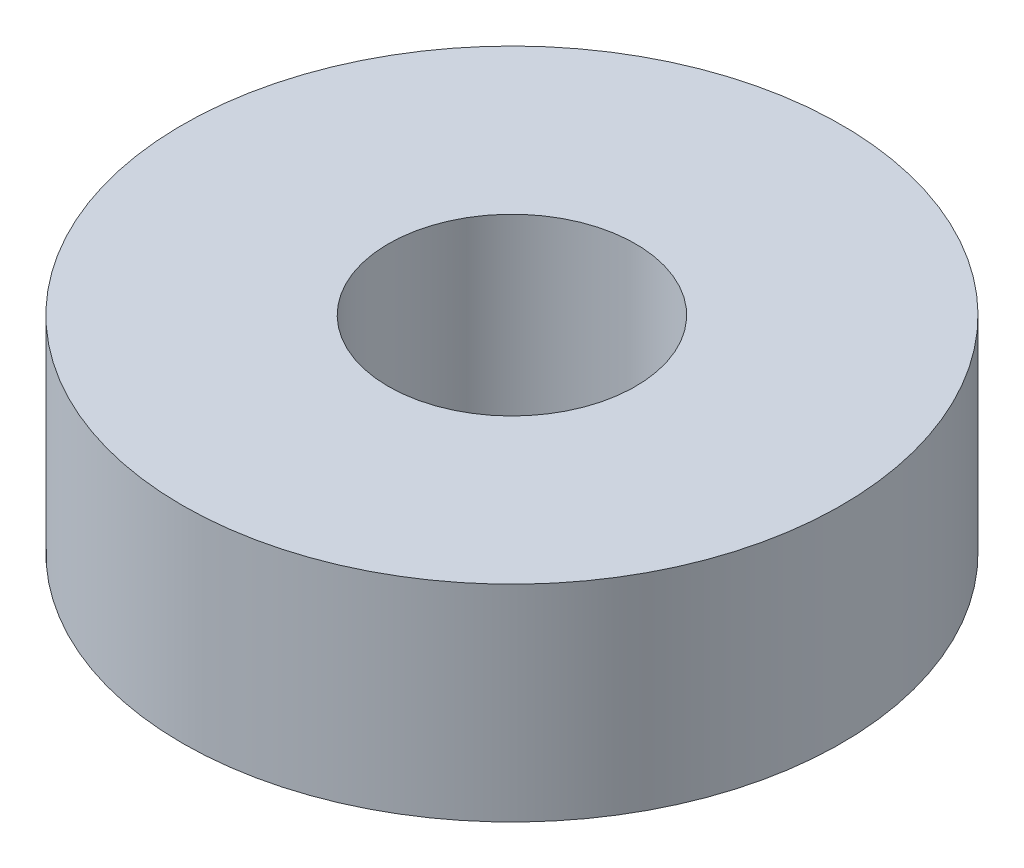
SolidWorks part; units mm, degrees
ref_plane "Front Plane" through (0, 0, 0) normal (0, 0, 1) x (1, 0, 0)
ref_plane "Top Plane" through (0, 0, 0) normal (0, 1, 0) x (1, 0, 0)
ref_plane "Right Plane" through (0, 0, 0) normal (1, 0, 0) x (0, 0, -1)
sketch "Sketch1" plane through (0, 0, 0) normal (0, 1, 0) x (1, 0, 0)
  circle A0 centre (0, 0) radius 8
  circle A1 centre (0, 0) radius 3
  dimension "D1" = 6
  dimension "D2" = 16
extrude "Boss-Extrude1" add sketch "Sketch1" along normal blind 5
